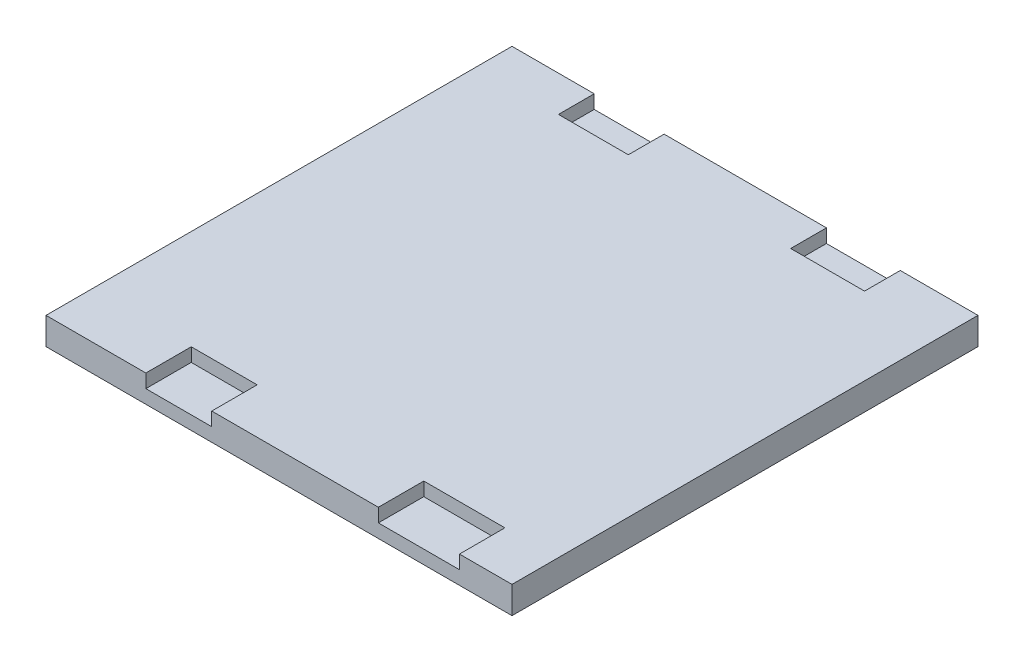
SolidWorks part; units mm, degrees
ref_plane "Front Plane" through (0, 0, 0) normal (0, 0, 1) x (1, 0, 0)
ref_plane "Top Plane" through (0, 0, 0) normal (0, 1, 0) x (1, 0, 0)
ref_plane "Right Plane" through (0, 0, 0) normal (1, 0, 0) x (0, 0, -1)
sketch "Sketch1" plane through (0, 0, 0) normal (0, 1, 0) x (1, 0, 0)
  line L1 (-69.85, -69.85) -> (69.85, -69.85)
  line L2 (-69.85, -69.85) -> (-69.85, 69.85)
  line L3 (-69.85, 69.85) -> (69.85, 69.85)
  line L4 (69.85, -69.85) -> (69.85, 69.85)
  line L5 (-69.85, -69.85) -> (69.85, 69.85) construction
  line L6 (-69.85, 69.85) -> (69.85, -69.85) construction
  point P0 (0, 0)
  dimension "D1" = 139.7
  dimension "D2" = 139.7
extrude "Boss-Extrude1" add sketch "Sketch1" along normal blind 4.064
sketch "Sketch2" plane through (0, 4.064, 0) normal (0, 1, 0) x (1, 0, 0)
  line L4 (24.4144, 69.85) -> (-24.2546, 69.85)
  line L6 (-45.201, 69.85) -> (-45.201, 59.1303)
  line L7 (-45.201, 59.1303) -> (-24.2546, 59.1303)
  line L8 (69.85, -69.85) -> (69.85, 69.85)
  line L9 (69.85, 69.85) -> (-69.85, 69.85)
  line L10 (-69.85, 69.85) -> (-69.85, -69.85)
  line L11 (-69.85, -69.85) -> (69.85, -69.85)
  line L12 (69.85, -69.85) -> (69.85, 69.85)
  line L14 (-69.85, 69.85) -> (-69.85, -69.85)
  line L16 (-24.2546, 69.85) -> (-24.2546, 59.1303)
  line L17 (69.85, 69.85) -> (46.5509, 69.85)
  line L18 (24.4144, 69.85) -> (24.4144, 59.1303)
  line L19 (24.4144, 59.1303) -> (46.5509, 59.1303)
  line L20 (46.5509, 69.85) -> (46.5509, 59.1303)
  line L22 (29.7889, -69.85) -> (29.7889, -56.2362)
  line L23 (29.7889, -56.2362) -> (54.1013, -56.2362)
  line L24 (54.1013, -69.85) -> (54.1013, -56.2362)
  line L26 (-20.1606, -69.85) -> (-20.1606, -56.2362)
  line L27 (-20.1606, -56.2362) -> (-39.917, -56.2362)
  line L28 (-39.917, -69.85) -> (-39.917, -56.2362)
  line L29 (-45.201, 69.85) -> (-69.85, 69.85)
  line L30 (-39.917, -69.85) -> (-69.85, -69.85)
  line L31 (-20.1606, -69.85) -> (29.7889, -69.85)
  line L32 (54.1013, -69.85) -> (69.85, -69.85)
  dimension "D1" = 0
extrude "Boss-Extrude2" add sketch "Sketch2" along normal blind 4.064
